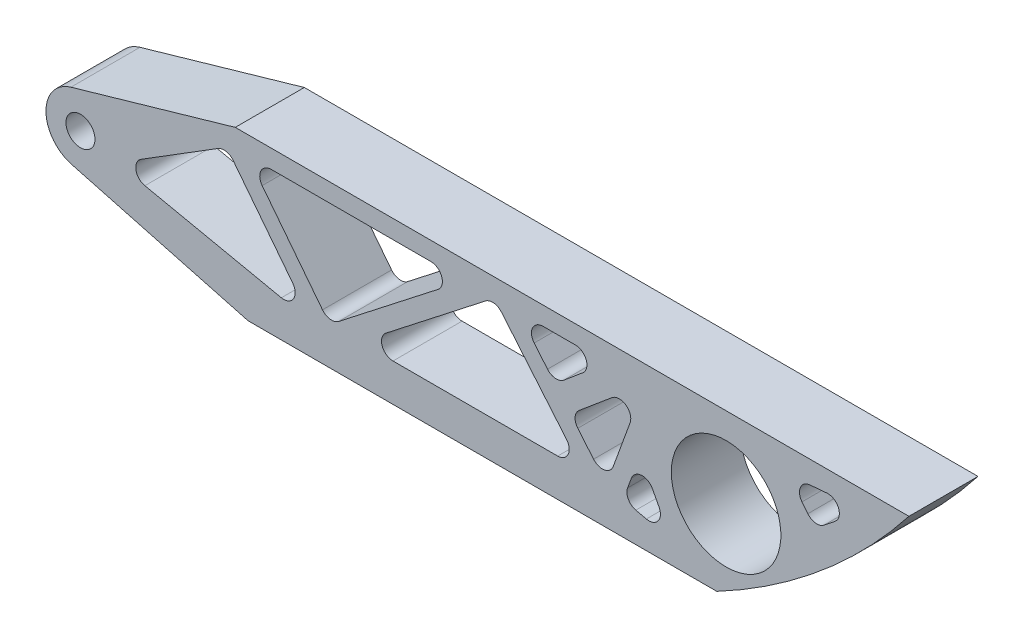
SolidWorks part; units mm, degrees
ref_plane "Front Plane" through (0, 0, 0) normal (0, 0, 1) x (1, 0, 0)
ref_plane "Top Plane" through (0, 0, 0) normal (0, 1, 0) x (1, 0, 0)
ref_plane "Right Plane" through (0, 0, 0) normal (1, 0, 0) x (0, 0, -1)
sketch "Sketch1" plane through (0, 0, 0) normal (0, 0, 1) x (1, 0, 0)
  line L1 (120.65, 22.225) -> (-120.65, 22.225)
  line L2 (120.65, 22.225) -> (120.65, -22.225)
  line L3 (120.65, -22.225) -> (-120.65, -22.225)
  line L4 (-120.65, 22.225) -> (-120.65, -22.225)
  line L5 (120.65, 22.225) -> (-120.65, -22.225) construction
  line L6 (120.65, -22.225) -> (-120.65, 22.225) construction
  point P0 (0, 0)
  dimension "D1" = 241.3
  dimension "D2" = 44.45
extrude "Boss-Extrude1" add sketch "Sketch1" along normal blind 19.06
sketch "Sketch3" plane through (0, 0, 19.06) normal (0, 0, 1) x (1, 0, 0)
  line L0 (0, 0) -> (-120.65, 0) construction
  line L1 (-120.65, 22.225) -> (-120.65, -22.225) construction
  circle A0 centre (-107.95, 0) radius 4
  dimension "D2" = 8
  dimension "D1" = 12.7
extrude "Cut-Extrude1" cut sketch "Sketch3" against normal through all
sketch "Sketch5" plane through (0, 0, 19.06) normal (0, 0, 1) x (1, 0, 0)
  line L0 (-120.65, -22.225) -> (120.65, -22.225) construction
  line L1 (-110.4107, -9.2017) -> (-61.7102, -22.225)
  line L2 (-110.5883, 9.1523) -> (-65.2393, 22.225)
  line L3 (120.65, 22.225) -> (-120.65, 22.225) construction
  line L4 (-65.2393, 22.225) -> (-120.65, 22.225)
  line L5 (-120.65, 22.225) -> (-120.65, -22.225)
  line L6 (-120.65, -22.225) -> (-61.7102, -22.225)
  line L7 (120.65, 22.225) -> (120.65, -22.225)
  line L8 (120.65, -22.225) -> (67.6371, -22.225)
  arc A0 (67.6371, -22.225) -> (120.65, 22.225) centre (-9.5799, 123.7049) ccw
  arc A2 (-110.5883, 9.1523) -> (-110.4107, -9.2017) centre (-107.95, 0) ccw
  line M3 (-120.65, 22.225) -> (-120.65, -22.225)
  line M4 (-120.65, -22.225) -> (120.65, -22.225)
  line M5 (120.65, -22.225) -> (120.65, 22.225)
  line M6 (120.65, 22.225) -> (-120.65, 22.225)
  dimension "D1" = 165.1
  dimension "D2" = 19.05
extrude "Cut-Extrude2" cut sketch "Sketch5" against normal through all contours A0 L8 M5 | A2 L2 L1 M6 M3 M4 region at (-86.2512, -16.4265, 19.06) region at (104.3043, -8.4634, 19.06)
sketch "Sketch6" plane through (0, 0, 19.06) normal (0, 0, 1) x (1, 0, 0)
  line L0 (-107.95, 0) -> (99.7595, 0) construction
  arc A0 (67.6371, -22.225) -> (120.65, 22.225) centre (-9.5799, 123.7049) ccw construction
sketch "Sketch11" plane through (0, 0, 0) normal (0, 0, -1) x (-1, 0, 0)
  line L1 (107.95, 0) -> (-99.7595, 0) construction
  circle A1 centre (-70.2, 0) radius 15.113
  circle A2 centre (107.95, 0) radius 4 construction
  dimension "D1" = 30.226
  dimension "D2" = 178.15
extrude "Cut-Extrude3" cut sketch "Sketch11" against normal through all
sketch "Sketch12" [suppressed] plane through (0, 0, 0) normal (0, 0, -1) x (-1, 0, 0)
  line L3 (62.1778, -29.4105) -> (46.0432, -22.2176)
  line L5 (46.0432, -22.2176) -> (70.9328, -9.772)
  line L6 (70.9328, -9.772) -> (62.1778, -29.4105)
  dimension "D1" = 90
extrude "Boss-Extrude2" [suppressed] add sketch "Sketch12" against normal up to surface (19.06 mm away) up to face at (55.087, 0, 19.06)
sketch "Sketch14" plane through (0, 0, 19.06) normal (0, 0, 1) x (1, 0, 0)
  line L0 (87.4273, 15.5587) -> (94.742, 6.4153)
  line L1 (94.742, 6.4153) -> (108.4371, 17.3503)
  line L2 (108.4371, 17.3503) -> (87.4273, 15.5587)
  line L3 (6.2381, 17.145) -> (30.5353, -11.846)
  line L4 (46.5104, -0.2633) -> (41.7978, -13.1718)
  line L5 (30.5353, -11.846) -> (-30.9487, -11.846)
  line L6 (-30.9487, -11.846) -> (6.2381, 17.145)
  line L7 (-2.0242, 17.145) -> (-61.8125, 17.145)
  line L8 (-61.8125, 17.145) -> (-39.211, -11.846)
  line L9 (-39.211, -11.846) -> (-2.0242, 17.145)
  line L10 (-67.5872, 16.2898) -> (-44.0189, -13.9413)
  line L11 (-44.0189, -13.9413) -> (-97.91, -2.5585)
  line L12 (-97.91, -2.5585) -> (-67.5872, 16.2898)
  line L13 (120.65, 22.225) -> (-65.2393, 22.225) construction
  line L14 (12.8663, 17.145) -> (22.9708, 5.0885)
  line L15 (22.9708, 5.0885) -> (37.3564, 17.145)
  line L16 (37.3564, 17.145) -> (12.8663, 17.145)
  line L17 (47.7718, 17.2115) -> (27.2354, 0)
  line L18 (-107.95, 0) -> (99.7595, 0) construction
  line L19 (27.2354, 0) -> (37.1635, -11.846)
  line L20 (37.1635, -11.846) -> (47.7718, 17.2115)
  line L21 (41.7978, -13.1718) -> (54.9817, -16.225)
  line L22 (54.9817, -16.225) -> (46.5104, -0.2633)
  dimension "D1" = 5.2446
  dimension "D2" = 5.08
  dimension "D3" = 5.08
  dimension "D4" = 5.08
  dimension "D5" = 37.8264
  dimension "D6" = 5.08
extrude "Cut-Extrude5" cut sketch "Sketch14" against normal through all
fillet "Fillet1" radius 3.175 21 edges at (-67.5872, 16.2898, 9.53) (-44.0189, -13.9413, 9.53) (-97.91, -2.5585, 9.53) (-61.8125, 17.145, 9.53) (-2.0242, 17.145, 9.53) (-39.211, -11.846, 9.53) (-30.9487, -11.846, 9.53) (6.2381, 17.145, 9.53) (30.5353, -11.846, 9.53) (87.4273, 15.5587, 9.53) (108.4371, 17.3503, 9.53) (94.742, 6.4153, 9.53) (47.7718, 17.2115, 9.53) (22.9708, 5.0885, 9.53) (37.3564, 17.145, 9.53) (12.8663, 17.145, 9.53) (27.2354, 0, 9.53) (37.1635, -11.846, 9.53) (46.5104, -0.2633, 9.53) (54.9817, -16.225, 9.53) (41.7978, -13.1718, 9.53)
sketch "Sketch15" plane through (0, 0, 0) normal (0, 0, -1) x (-1, 0, 0)
  line L0 (61.7102, -22.225) -> (117.4746, -22.225) construction
  line L1 (117.4746, -22.225) -> (117.4746, -0.0922) construction
  arc A0 (110.4107, -9.2017) -> (110.5883, 9.1523) centre (107.95, 0) ccw construction
